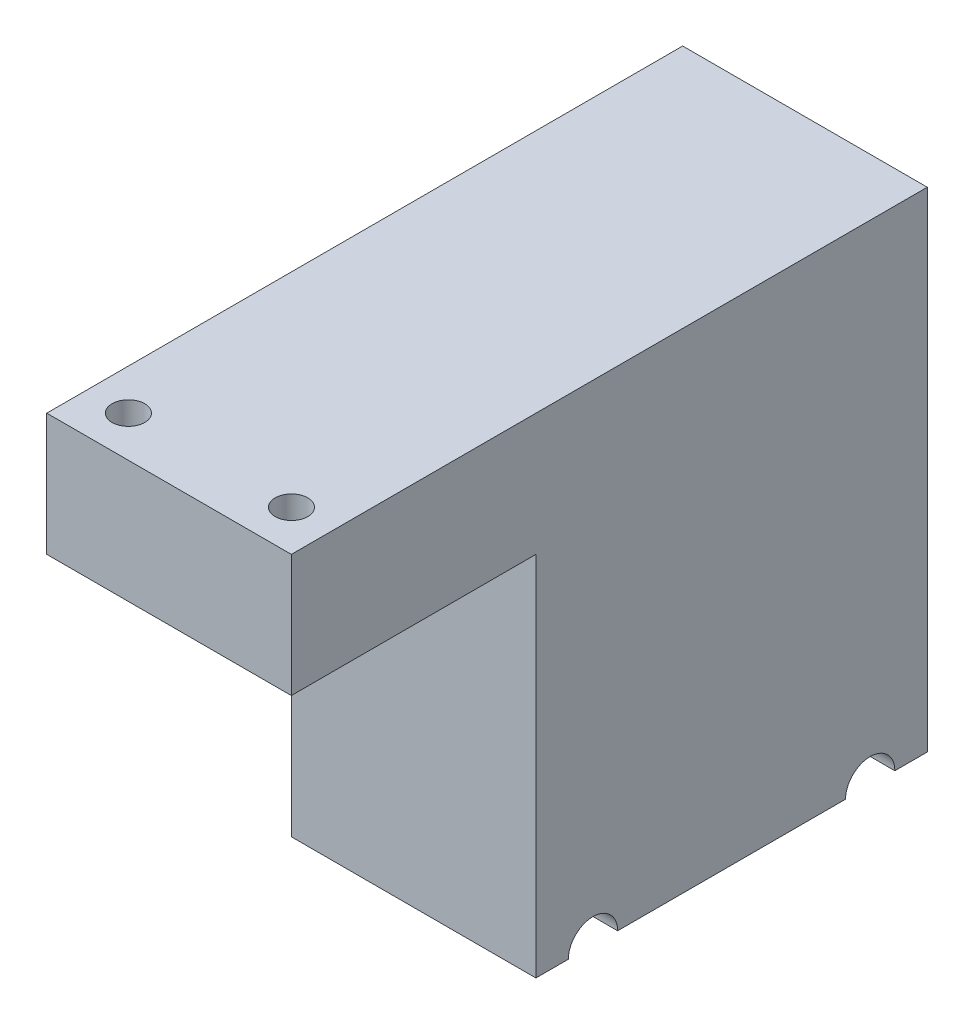
SolidWorks part; units mm, degrees
ref_plane "前视基准面" through (0, 0, 0) normal (0, 0, 1) x (1, 0, 0)
ref_plane "上视基准面" through (0, 0, 0) normal (0, 1, 0) x (1, 0, 0)
ref_plane "右视基准面" through (0, 0, 0) normal (1, 0, 0) x (0, 0, -1)
sketch "草图1" plane through (0, 0, 0) normal (0, 0, 1) x (1, 0, 0)
  line L1 (0, 0) -> (30, 0)
  line L2 (0, 0) -> (0, 95)
  line L3 (0, 95) -> (30, 95)
  line L4 (30, 0) -> (30, 95)
extrude "凸台-拉伸1" add sketch "草图1" along normal blind 48
sketch "草图2" plane through (0, 0, 0) normal (-1, 0, 0) x (0, 0, 1)
  line L1 (48, 95) -> (48, 0) construction
  line L2 (48, 0) -> (0, 0) construction
  circle A0 centre (7, 35) radius 3.005
  circle A1 centre (41, 35) radius 3.005
  circle A2 centre (7, 35) radius 3.025
  circle A3 centre (41, 35) radius 3.025
  dimension "D3" = 6.01
  dimension "D1" = 34
  dimension "D2" = 7
  dimension "D5" = 35
  dimension "D6" = 35
  dimension "D4" = 0.02
extrude "切除-拉伸1" cut sketch "草图2" against normal blind 46 body kept at (0, 0, 0)
sketch "草图3" plane through (0, 0, 48) normal (0, 0, 1) x (1, 0, 0)
  line L0 (30, 0) -> (30, 95) construction
  line L1 (0, 95) -> (30, 95)
  line L2 (0, 95) -> (0, 80)
  line L3 (0, 80) -> (30, 80)
  line L4 (30, 95) -> (30, 80)
extrude "凸台-拉伸2" add sketch "草图3" along normal blind 30
sketch "草图4" plane through (0, 95, 0) normal (0, 1, 0) x (1, 0, 0)
  line L0 (30, -78) -> (30, 0) construction
  line L1 (0, -78) -> (0, 0) construction
  circle A0 centre (5, -72.9837) radius 2
  circle A2 centre (25, -72.9837) radius 2
  dimension "D1" = 4
  dimension "D2" = 5
  dimension "D3" = 20
  dimension "D5" = 5
extrude "切除-拉伸2" cut sketch "草图4" against normal blind 5
sketch "草图5" plane through (0, 0, 0) normal (-1, 0, 0) x (0, 0, 1)
  line L0 (0, 95) -> (0, 0) construction
  line L1 (0, 35) -> (48, 35)
  line L2 (0, 35) -> (0, 0)
  line L3 (0, 0) -> (48, 0)
  line L4 (48, 35) -> (48, 0)
extrude "切除-拉伸3" cut sketch "草图5" against normal through all
sketch "草图6" plane through (0, 35, 0) normal (0, -1, 0) x (1, 0, 0)
  line L0 (0, 37.975) -> (0, 10.025) construction
  line L1 (0, 37.975) -> (30, 37.975) construction
  line L3 (30, 10.025) -> (0, 10.025) construction
  circle A0 centre (6, 31.975) radius 2
  circle A3 centre (24, 31.975) radius 2
  circle A4 centre (6, 16.025) radius 2
  circle A7 centre (24, 16.025) radius 2
  dimension "D1" = 4
  dimension "D3" = 18
  dimension "D7" = 6
  dimension "D6" = 6
  dimension "D2" = 6
extrude "切除-拉伸4" cut sketch "草图6" against normal blind 5
